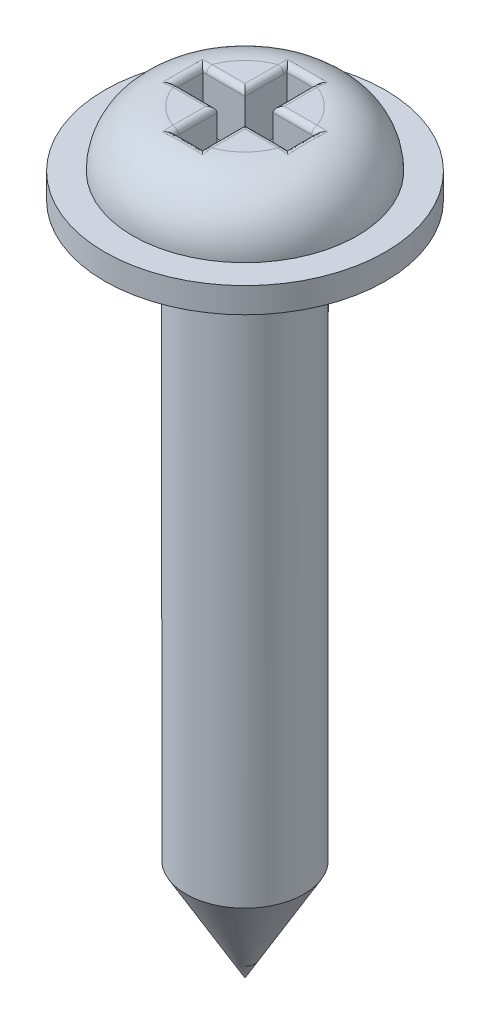
SolidWorks part; units mm, degrees
ref_plane "Front Plane" through (0, 0, 0) normal (0, 0, 1) x (1, 0, 0)
ref_plane "Top Plane" through (0, 0, 0) normal (0, 1, 0) x (1, 0, 0)
ref_plane "Right Plane" through (0, 0, 0) normal (1, 0, 0) x (0, 0, -1)
sketch "Sketch1" plane through (0, 0, 0) normal (0, 1, 0) x (1, 0, 0)
  circle A0 centre (0, 0) radius 2.5
  dimension "D1" = 5
extrude "Boss-Extrude1" add sketch "Sketch1" along normal blind 0.45
sketch "Sketch3" plane through (0, 0.45, 0) normal (0, 1, 0) x (1, 0, 0)
  circle A0 centre (0, 0) radius 2
  dimension "D1" = 4
extrude "Boss-Extrude2" add sketch "Sketch3" along normal blind 1
fillet "Fillet1" radius 1 1 edges at (0, 1.45, 2)
sketch "Sketch4" plane through (0, 1.45, 0) normal (0, 1, 0) x (1, 0, 0)
  line L0 (-1, 0) -> (1, 0) construction
  line L1 (0, 1) -> (0, -1) construction
  line L2 (-1, -0.25) -> (-0.25, -0.25)
  line L3 (-0.25, 1) -> (-0.25, 0.25)
  line L4 (-1, 0.25) -> (-0.25, 0.25)
  line L5 (0.25, 1) -> (0.25, 0.25)
  line L6 (0.25, 1) -> (-0.25, 1)
  line L7 (0.25, -1) -> (-0.25, -1)
  line L8 (1, 0.25) -> (1, -0.25)
  line L9 (-1, 0.25) -> (-1, -0.25)
  line L10 (0.25, 0.25) -> (1, 0.25)
  line L11 (-1, 0.25) -> (1, 0.25) construction
  line L12 (0.25, -0.25) -> (0.25, -1)
  line L13 (0.25, 1) -> (0.25, -1) construction
  line L14 (0.25, -0.25) -> (1, -0.25)
  line L15 (-1, -0.25) -> (1, -0.25) construction
  line L16 (-0.25, -0.25) -> (-0.25, -1)
  line L17 (-0.25, 1) -> (-0.25, -1) construction
  point P4 (0, 0)
  point P10 (0, 0)
  dimension "D1" = 2
  dimension "D2" = 2
  dimension "D3" = 0.25
  dimension "D4" = 0.25
extrude "Cut-Extrude1" cut sketch "Sketch4" against normal blind 1
fillet "Fillet2" radius 0.1 20 edges at (0.25, 1.45, -0.6091) (-0.25, 1.45, 0.6091) (0.6091, 1.45, -0.25) (0.6091, 1.45, 0.25) (0.25, 1.45, 0.6091) (-0.6091, 1.45, 0.25) (-0.6091, 1.45, -0.25) (-0.25, 1.45, -0.6091)
sketch "Sketch5" plane through (0, 0, 0) normal (0, -1, 0) x (1, 0, 0)
  circle A0 centre (0, 0) radius 1.05
  dimension "D1" = 2.1
extrude "Boss-Extrude3" add sketch "Sketch5" along normal blind 12
chamfer "Chamfer1" distance 1.05 angle 60 1 edges at (0, -12, -1.05) first distance on face at (0, -12, -1.05)
